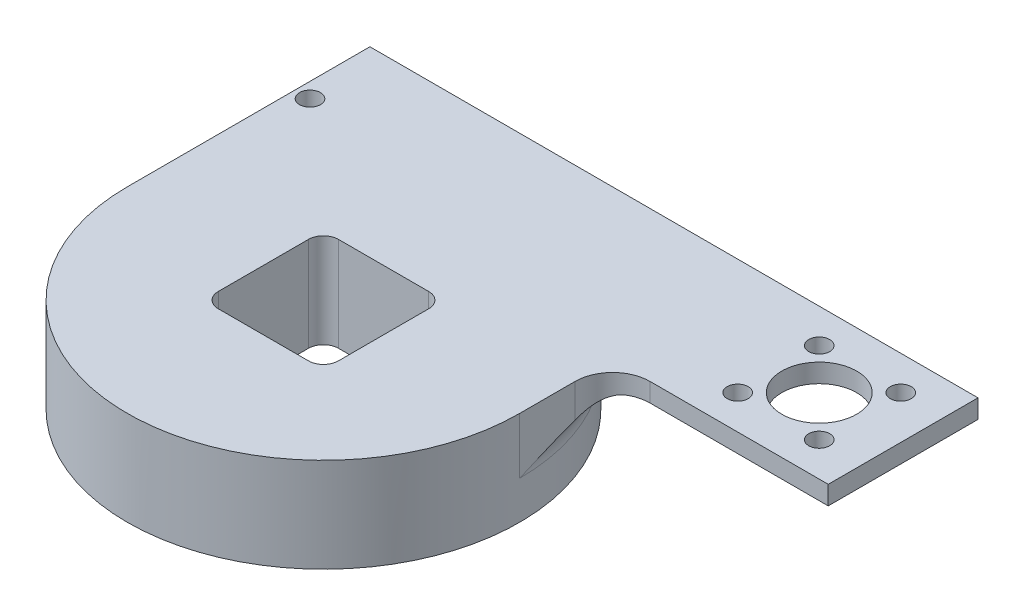
SolidWorks part; units mm, degrees
ref_plane "Front Plane" through (0, 0, 0) normal (0, 0, 1) x (1, 0, 0)
ref_plane "Top Plane" through (0, 0, 0) normal (0, 1, 0) x (1, 0, 0)
ref_plane "Right Plane" through (0, 0, 0) normal (1, 0, 0) x (0, 0, -1)
sketch "Sketch1" plane through (0, 0, 0) normal (0, 1, 0) x (1, 0, 0)
  line L0 (-1.1049, 0) -> (-33.274, 0) construction
  line L1 (-1.1049, 0) -> (33.274, 0) construction
  circle A0 centre (0, 0) radius 33.274
extrude "Boss-Extrude1" add sketch "Sketch1" along normal blind 16.002
sketch "Sketch2" plane through (0, 16.002, 0) normal (0, 1, 0) x (1, 0, 0)
  line L0 (0, 0) -> (-33.274, 0) construction
  line L1 (0, 0) -> (33.274, 0) construction
  line L2 (-33.274, 0) -> (-33.274, 41.148)
  line L3 (-33.274, 41.148) -> (69.85, 41.148)
  line L4 (69.85, 41.148) -> (69.85, 15.748)
  line L5 (33.274, 0) -> (33.274, 15.748)
  line L6 (33.274, 15.748) -> (69.85, 15.748)
  circle A0 centre (0, 0) radius 33.274 construction
  circle A2 centre (0, 0) radius 33.274
  arc A3 (-33.274, 0) -> (33.274, 0) centre (0, 0) ccw
  dimension "D1" = 0
extrude "Boss-Extrude2" add sketch "Sketch2" against normal blind 3.175
fillet "Fillet1" radius 6.35 1 edges at (0, 12.827, -33.274)
fillet "Fillet2" radius 6.35 1 edges at (33.274, 14.0863, -15.748)
sketch "Sketch3" plane through (0, 16.002, 0) normal (0, 1, 0) x (1, 0, 0)
  line L2 (-33.274, 41.148) -> (-33.274, 28.448) construction
  line L3 (-33.274, 41.148) -> (-33.274, 0) construction
  line L4 (-33.274, 28.448) -> (-30.734, 28.448) construction
  circle A0 centre (-30.734, 28.448) radius 1.778
extrude "Cut-Extrude1" cut sketch "Sketch3" against normal up to next
sketch "Sketch4" plane through (0, 16.002, 0) normal (0, 1, 0) x (1, 0, 0)
  line L0 (69.85, 41.148) -> (45.466, 41.148) construction
  line L1 (69.85, 41.148) -> (-33.274, 41.148) construction
  line L2 (45.466, 41.148) -> (45.466, 28.448) construction
  line L3 (45.466, 28.448) -> (65.786, 28.448) construction
  line L4 (55.626, 28.448) -> (62.5408, 35.3628) construction
  line L5 (55.626, 28.448) -> (62.5408, 21.5332) construction
  line L6 (55.626, 28.448) -> (48.7112, 21.5332) construction
  line L7 (55.626, 28.448) -> (48.7112, 35.3628) construction
  circle A0 centre (48.7112, 35.3628) radius 1.778
  circle A1 centre (62.5408, 35.3628) radius 1.778
  circle A2 centre (62.5408, 21.5332) radius 1.778
  circle A3 centre (55.626, 28.448) radius 6.35
  circle A4 centre (48.7112, 21.5332) radius 1.778
extrude "Cut-Extrude2" cut sketch "Sketch4" against normal up to next
sketch "Sketch5" plane through (0, 16.002, 0) normal (0, 1, 0) x (1, 0, 0)
  line L1 (10.1926, 10.1926) -> (-10.1926, 10.1926)
  line L2 (10.1926, 10.1926) -> (10.1926, -10.1926)
  line L3 (10.1926, -10.1926) -> (-10.1926, -10.1926)
  line L4 (-10.1926, 10.1926) -> (-10.1926, -10.1926)
  line L5 (10.1926, 10.1926) -> (-10.1926, -10.1926) construction
  line L6 (10.1926, -10.1926) -> (-10.1926, 10.1926) construction
  point P0 (0, 0)
  dimension "D1" = 28.829
extrude "Cut-Extrude3" cut sketch "Sketch5" against normal up to next
fillet "Fillet3" radius 2.54 1 edges at (-10.1926, 8.001, -10.1926)
fillet "Fillet4" radius 2.54 1 edges at (10.1926, 8.001, -10.1926)
fillet "Fillet5" radius 2.54 1 edges at (10.1926, 8.001, 10.1926)
fillet "Fillet6" radius 2.54 1 edges at (-10.1926, 8.001, 10.1926)
